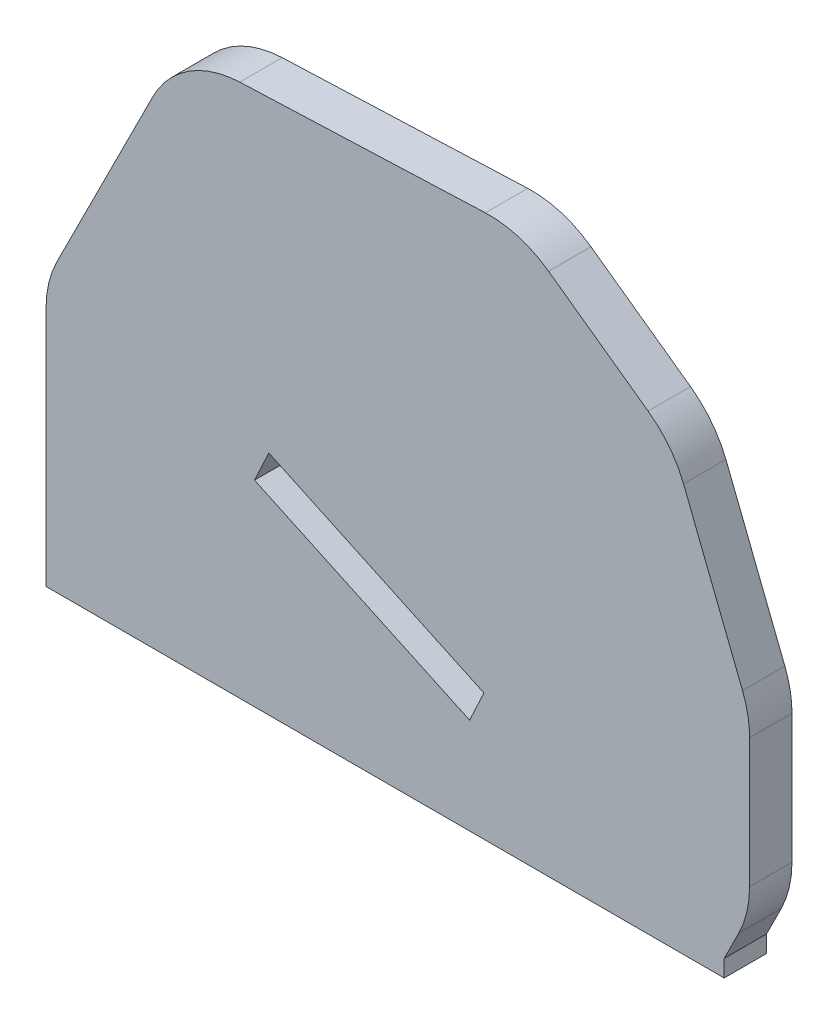
SolidWorks part; units mm, degrees
material "PBT General Purpose"
ref_plane "Front Plane" through (0, 0, 0) normal (0, 0, 1) x (1, 0, 0)
ref_plane "Top Plane" through (0, 0, 0) normal (0, 1, 0) x (1, 0, 0)
ref_plane "Right Plane" through (0, 0, 0) normal (1, 0, 0) x (0, 0, -1)
sketch "frame_outline" plane through (0, 0, 0) normal (0, 0, 1) x (1, 0, 0)
  line L0 (0, 0) -> (4, 0)
  line L1 (4, 0) -> (4, 0.1)
  line L2 (4, 0.1) -> (4.15, 0.4)
  line L3 (4.15, 0.4) -> (4.15, 1.4161)
  line L19 (4.15, 1.4161) -> (3.6952, 2.5687)
  line L20 (3.6952, 2.5687) -> (2.7971, 3.2123)
  line L21 (2.7971, 3.2123) -> (0.7894, 3.134)
  line L62 (0.7894, 3.134) -> (0, 1.5628)
  line L63 (0, 1.5628) -> (0, 0)
  line L64 (1.2298, 1.1578) -> (2.4986, 0.5662)
  line L65 (1.2298, 1.1578) -> (1.3143, 1.3391)
  line L66 (2.4986, 0.5662) -> (2.5831, 0.7474)
  line L67 (1.3143, 1.3391) -> (2.5831, 0.7474)
  line L68 (1.272, 1.2484) -> (2.5409, 0.6568) construction
  dimension "D1" = 4
  dimension "D6" = 0.1
  dimension "D7" = 0.15
  dimension "D8" = 0.3
  dimension "D12" = 0.2
  dimension "D13" = 1.4
  dimension "D14" = 25
  dimension "D3" = 1.6
extrude "Boss-Extrude1" add sketch "frame_outline" along normal mid plane 0.25
fillet "Fillet1" radius 0.6 6 edges at (4.15, 0.4, 0) (4.15, 1.4161, 0) (3.6952, 2.5687, 0) (2.7971, 3.2123, 0) (0.7894, 3.134, 0) (0, 1.5628, 0)
equation "\"t\"= 0.25'thickness of the sheets"
equation "\"t_cf\" = 0.115'thickness of single carbon fiber layer"
equation "\"t_kapton\" = 0.025'thickness of single Kapton flex layer"
equation "\"t_fr4\" = 0.1'thickness of FR4 with copper layer"
equation "\"joint_flex\"= 0.1'Width of flextures gap"
equation "\"joint_flex_eff\"= 0.02'Width of flecture after castelation"
equation "\"joint_fold\"= 0.2'Width of folding joints for 90deg fold"
equation "\"gap_tolerance\"= 0.002'Width to have interfecence fit between carbon fiber inserts"
equation "\"assemble_angle\"= 90'Angle of assembly parts"
equation "\"D1@Boss-Extrude1\"=\"t\""
equation "\"D12@frame_outline\"=\"t_fr4\"*2"
equation "\"link_lift\"= 0.5'Actuation linkage amplification for the lift motion"
equation "\"link_swing\"= 0.45'Actuation linkage amplification for the swing motion"
